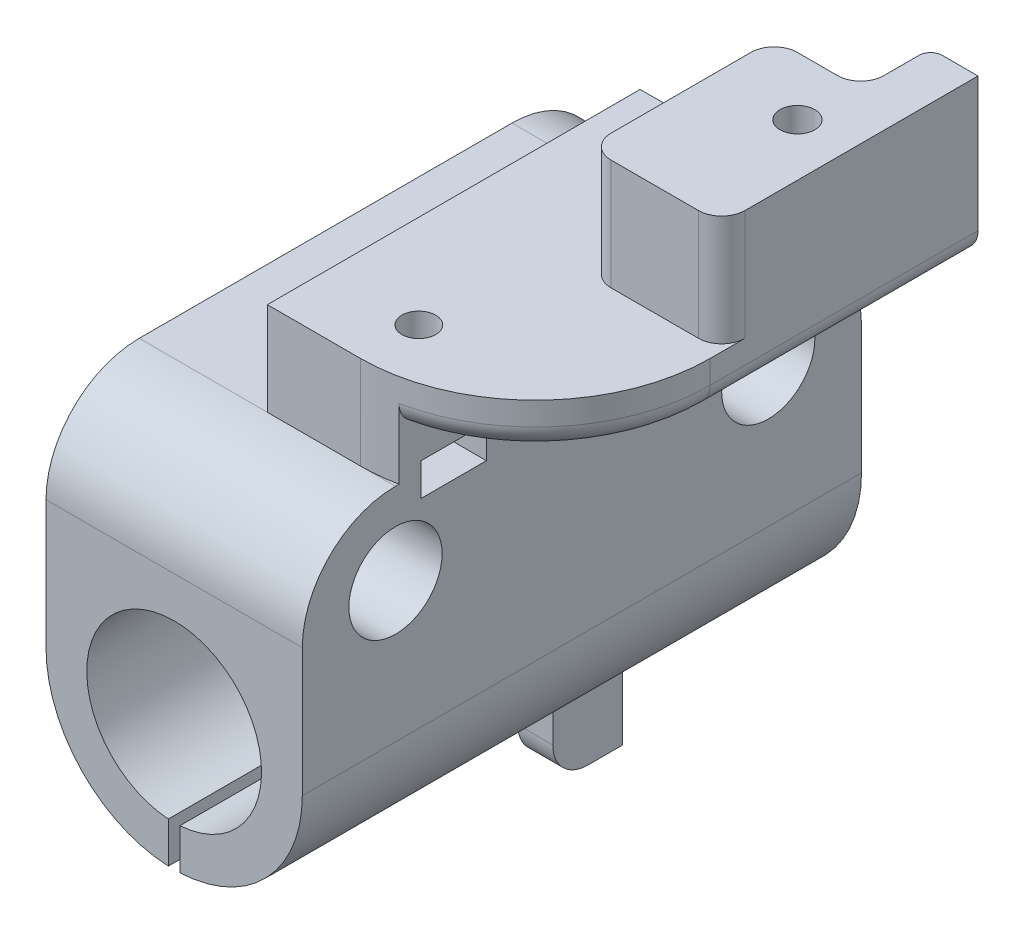
SolidWorks part; units mm, degrees
ref_plane "Спереди" through (0, 0, 0) normal (0, 0, 1) x (1, 0, 0)
ref_plane "Сверху" through (0, 0, 0) normal (0, 1, 0) x (1, 0, 0)
ref_plane "Справа" through (0, 0, 0) normal (1, 0, 0) x (0, 0, -1)
sketch "Эскиз2" plane through (0, 0, 0) normal (0, 0, 1) x (1, 0, 0)
  line L0 (0, 11) -> (0, 7.5) construction
  line L4 (0.5, -7.4833) -> (0.5, -10.9886)
  line L7 (-11, 0) -> (-11, 27)
  line L8 (-0.5, -7.4833) -> (-0.5, -10.9886)
  line L11 (-11, 27) -> (11, 27)
  line L12 (11, 0) -> (11, 27)
  arc A0 (0.5, -7.4833) -> (-0.5, -7.4833) centre (0, 0) ccw
  arc A2 (-11, 0) -> (-0.5, -10.9886) centre (0, 0) ccw
  arc A9 (0.5, -10.9886) -> (11, 0) centre (0, 0) ccw
  dimension "D1" = 15
  dimension "D4" = 0.5
  dimension "D6" = 0.5
  dimension "D11" = 27
extrude "Бобышка-Вытянуть1" add sketch "Эскиз2" along normal blind 48
sketch "Эскиз3" plane through (11, 0, 0) normal (1, 0, 0) x (0, 0, -1)
  line L0 (-48, 0) -> (-48, 27) construction
  line L1 (-48, 27) -> (0, 27) construction
  circle A0 centre (-40, 12) radius 4
  dimension "D1" = 8
  dimension "D2" = 8
  dimension "D3" = 15
extrude "Вырез-Вытянуть1" cut sketch "Эскиз3" against normal through all both and the other way through all
sketch "Эскиз4" plane through (11, 0, 0) normal (1, 0, 0) x (0, 0, -1)
  line L3 (0, 0) -> (0, 27) construction
  line L4 (-48, 27) -> (0, 27) construction
  circle A0 centre (-8, 12) radius 4
  point P4 (0, 13.5)
  dimension "D1" = 8
  dimension "D2" = 8
  dimension "D3" = 15
extrude "Вырез-Вытянуть2" cut sketch "Эскиз4" against normal through all both and the other way through all
sketch "Эскиз5" plane through (11, 0, 0) normal (1, 0, 0) x (0, 0, -1)
  line L0 (0, 0) -> (0, 27) construction
  line L1 (-48, 27) -> (0, 27)
  line L2 (-48, 27) -> (-48, 23)
  line L3 (-48, 23) -> (0, 23)
  line L4 (0, 27) -> (0, 23)
  dimension "D1" = 4
extrude "Бобышка-Вытянуть3" add sketch "Эскиз5" along normal blind 12
sketch "Эскиз7" plane through (0, 27, 0) normal (0, 1, 0) x (1, 0, 0)
  line L1 (23, 0) -> (23, -48) construction
  line L2 (23, -24) -> (-11, -24) construction
  line L3 (-11, -48) -> (-11, 0) construction
  line L4 (23, 0) -> (-11, 0) construction
  line L5 (23, -48) -> (-11, -48) construction
  circle A0 centre (8, -35) radius 1.45
  circle A1 centre (18.5, -13) radius 1.45
  dimension "D1" = 2.9
  dimension "D2" = 13
  dimension "D3" = 29.5
  dimension "D4" = 2.9
  dimension "D5" = 13
  dimension "D6" = 19
extrude "Вырез-Вытянуть3" cut sketch "Эскиз7" against normal blind 25 and the other way through all from offset 15
sketch "Эскиз8" plane through (0, 27, 0) normal (0, 1, 0) x (1, 0, 0)
  line L0 (23, -24) -> (1.415, -24) construction
  line L1 (23, -48) -> (20, -48)
  line L2 (23, -48) -> (23, -45)
  line L3 (23, 0) -> (23, -48) construction
  line L4 (23, 0) -> (23, -3)
  line L5 (23, 0) -> (20, 0)
  arc A0 (20, -48) -> (23, -45) centre (20, -45) ccw
  arc A1 (20, 0) -> (23, -3) centre (20, -3) cw
  dimension "D3" = 6
  dimension "D4" = 3
extrude "Вырез-Вытянуть4" cut sketch "Эскиз8" against normal through all both and the other way through all
sketch "Эскиз9" plane through (0, 27, 0) normal (0, 1, 0) x (1, 0, 0)
  line L0 (23, -3) -> (23, -45) construction
  line L1 (-11, -48) -> (23, -48)
  line L2 (-11, -48) -> (-11, -40)
  line L3 (0, -40) -> (23, -40)
  line L4 (23, -48) -> (23, -40)
  line L5 (23, -24) -> (-11, -24) construction
  line L6 (-11, -48) -> (-11, 0) construction
  line L7 (-11, 0) -> (-11, -8)
  line L8 (-11, 0) -> (23, 0)
  line L9 (23, 0) -> (23, -8)
  line L10 (0, -8) -> (23, -8)
  line L13 (-11, -40) -> (-11, -8)
  line L15 (0, -40) -> (0, -8)
  dimension "D1" = 8
extrude "Вырез-Вытянуть5" cut sketch "Эскиз9" against normal blind 8
sketch "Эскиз10" plane through (0, 19, 0) normal (0, 1, 0) x (1, 0, 0)
  line L0 (0, -24) -> (-11, -24) construction
  line L1 (0, -40) -> (0, -8) construction
  line L2 (-11, 0) -> (-11, -48) construction
  circle A0 centre (-5.5, -24) radius 1.5
  dimension "D1" = 3
  dimension "D2" = 5.5
extrude "Вырез-Вытянуть6" cut sketch "Эскиз10" against normal blind 10
sketch "Эскиз11" plane through (-11, 0, 0) normal (-1, 0, 0) x (0, 0, 1)
  line L0 (24, 19) -> (24, 11.2) construction
  line L1 (0, 19) -> (48, 19) construction
  line L4 (21.2, 14) -> (26.8, 14)
  line L5 (21.2, 14) -> (21.2, 11.2)
  line L6 (21.2, 11.2) -> (26.8, 11.2)
  line L7 (26.8, 14) -> (26.8, 11.2)
  dimension "D1" = 2.8
  dimension "D2" = 5.6
  dimension "D3" = 2.8
  dimension "D4" = 5
extrude "Вырез-Вытянуть7" cut sketch "Эскиз11" against normal blind 10
sketch "Эскиз13" plane through (0, 27, 0) normal (0, 1, 0) x (1, 0, 0)
  line L1 (21, -8) -> (13.5, -8)
  line L2 (23, -10) -> (23, -22)
  line L3 (21, -24) -> (13.5, -24)
  line L4 (11.5, -10) -> (11.5, -22)
  line L6 (23, -10) -> (23, -8)
  line L7 (23, -8) -> (21, -8)
  arc A0 (23, -22) -> (21, -24) centre (21, -22) cw
  arc A1 (13.5, -24) -> (11.5, -22) centre (13.5, -22) cw
  arc A2 (13.5, -8) -> (11.5, -10) centre (13.5, -10) ccw
  circle A4 centre (18.5, -13) radius 1.5
  point P9 (11.5, -24)
  point P12 (11.5, -8)
  point P15 (23, -8)
  dimension "D3" = 2
  dimension "D1" = 16
  dimension "D2" = 11.5
extrude "Бобышка-Вытянуть4" add sketch "Эскиз13" along normal blind 9.5
fillet "Скругление2" radius 15 1 edges at (23, 25, 40)
fillet "Скругление4" radius 8 2 edges at (0, 19, 48) (0, 19, 0)
fillet "Скругление5" radius 2 2 edges at (23, 23, 16.5) (19.619, 23, 34.4868)
sketch "Эскиз14" plane through (0, 0, 8) normal (0, 0, -1) x (-1, 0, 0)
  line L0 (-11, 23) -> (-21, 23) construction
  line L1 (-23, 36.5) -> (-18.9331, 36.5)
  line L2 (-23, 36.5) -> (-23, 25)
  line L3 (-21, 23) -> (-18.9331, 23)
  line L4 (-18.9331, 36.5) -> (-18.9331, 23)
  arc A0 (-23, 25) -> (-21, 23) centre (-21, 25) ccw
  dimension "D1" = 2
extrude "Бобышка-Вытянуть5" add sketch "Эскиз14" along normal blind 6
fillet "Скругление6" radius 2 1 edges at (18.9331, 29.75, 8)
fillet "Скругление7" radius 1 1 edges at (18.9331, 29.75, 2)
sketch "Эскиз15" plane through (0, 0, 0) normal (0, 0, -1) x (-1, 0, 0)
  line L1 (0.5, -7.4833) -> (3.5, -7.4833)
  line L2 (0.5, -7.4833) -> (0.5, -21.4833)
  line L3 (0.5, -21.4833) -> (3.5, -21.4833)
  line L4 (3.5, -7.4833) -> (3.5, -21.4833)
  dimension "D1" = 14
  dimension "D2" = 3
extrude "Бобышка-Вытянуть6" add sketch "Эскиз15" against normal blind 6 from offset 9 offset against normal yes
fillet "Скругление8" radius 3 1 edges at (-2, -21.4833, 15)
sketch "Эскиз16" plane through (11, 0, 0) normal (1, 0, 0) x (0, 0, -1)
  line L1 (-35, 20.9071) -> (-35, 17) construction
  line L2 (-37.8, 19.8) -> (-32.2, 19.8)
  line L3 (-37.8, 19.8) -> (-37.8, 17)
  line L4 (-37.8, 17) -> (-32.2, 17)
  line L5 (-32.2, 19.8) -> (-32.2, 17)
  line L6 (-33.55, 17) -> (-36.45, 17) construction
  point P10 (-35, 17)
  point P12 (-35.0168, 16.3963)
  dimension "D1" = 2.8
  dimension "D2" = 5.6
  dimension "D3" = 2.8
extrude "Вырез-Вытянуть8" cut sketch "Эскиз16" against normal blind 7
sketch "Эскиз19" plane through (0, 23, 0) normal (0, -1, 0) x (1, 0, 0)
  line L9 (18.5, 16.1754) -> (15.75, 14.5877)
  line L10 (15.75, 14.5877) -> (15.75, 11.4123)
  line L11 (15.75, 11.4123) -> (18.5, 9.8246)
  line L12 (18.5, 9.8246) -> (21.25, 11.4123)
  line L13 (21.25, 11.4123) -> (21.25, 14.5877)
  line L14 (21.25, 14.5877) -> (18.5, 16.1754)
  circle A0 centre (18.5, 13) radius 2.75 construction
  point P0 (0, 0)
extrude "Вырез-Вытянуть9" cut sketch "Эскиз19" against normal blind 2.5 draft 5
